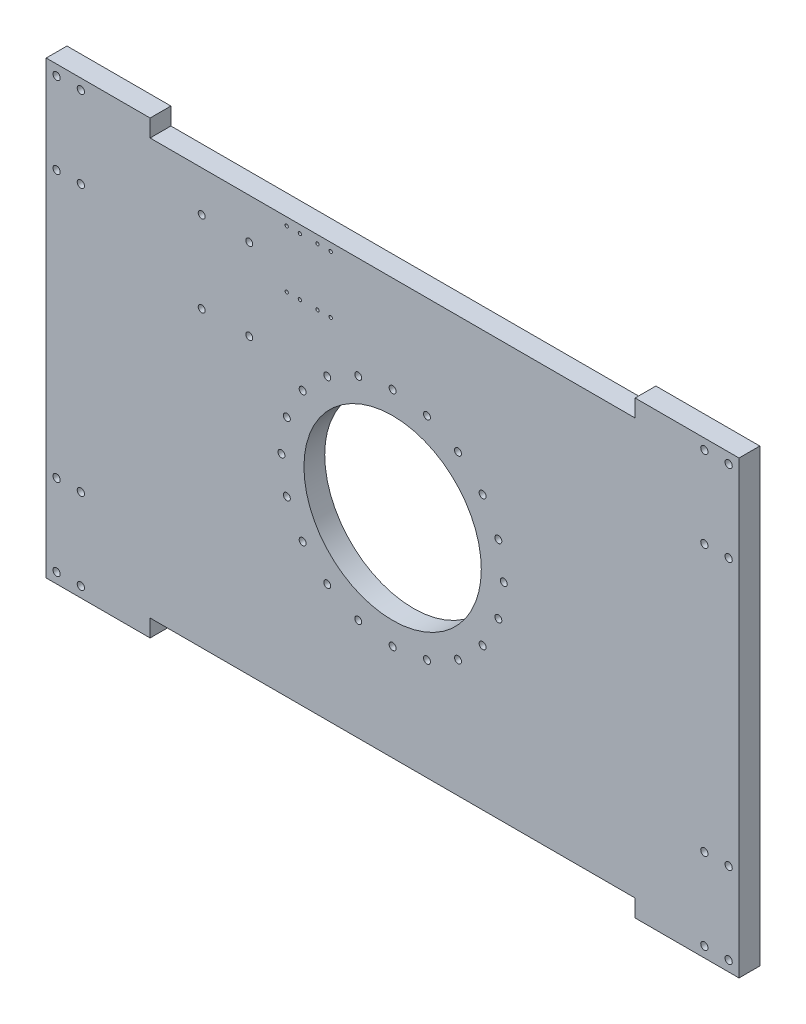
SolidWorks part; units mm, degrees
material "ASTM A36 Acier"
ref_plane "Plan de face" through (0, 0, 0) normal (0, 0, 1) x (1, 0, 0)
ref_plane "Plan de dessus" through (0, 0, 0) normal (0, 1, 0) x (1, 0, 0)
ref_plane "Plan de droite" through (0, 0, 0) normal (1, 0, 0) x (0, 0, -1)
sketch "Esquisse1" plane through (0, 0, 0) normal (0, 0, 1) x (1, 0, 0)
  line L0 (-1000, 1250) -> (-700, 1250)
  line L1 (-700, 1250) -> (-700, 1200)
  line L2 (-700, 1200) -> (700, 1200)
  line L3 (700, 1200) -> (700, 1250)
  line L4 (700, 1250) -> (1000, 1250)
  line L5 (1000, 1250) -> (1000, -50)
  line L6 (1000, -50) -> (700, -50)
  line L7 (700, -50) -> (700, 0)
  line L8 (700, 0) -> (-700, 0)
  line L9 (-700, 0) -> (-700, -50)
  line L10 (-700, -50) -> (-1000, -50)
  line L11 (-1000, -50) -> (-1000, 1250)
  line L13 (-970, -20) -> (-900, -20) construction
  line L14 (-970, -20) -> (-970, 215) construction
  line L15 (-970, 215) -> (-900, 215) construction
  line L16 (-900, -20) -> (-900, 215) construction
  circle A0 centre (-970, -20) radius 10.5
  circle A1 centre (-970, 215) radius 10.5
  circle A2 centre (-900, 215) radius 10.5
  circle A3 centre (-900, -20) radius 10.5
  point P15 (0, 0)
  dimension "D3" = 30
  dimension "D14" = 21
  dimension "D15" = 21
  dimension "D16" = 21
  dimension "D17" = 21
  dimension "D1" = 2000
  dimension "D2" = 50
  dimension "D4" = 300
  dimension "D5" = 300
  dimension "D6" = 300
  dimension "D7" = 300
  dimension "D8" = 1200
  dimension "D9" = 50
  dimension "D10" = 1400
  dimension "D11" = 30
  dimension "D12" = 70
  dimension "D13" = 235
extrude "Boss.-Extru.1" add sketch "Esquisse1" along normal blind 60
sketch "Esquisse2" plane through (0, 0, 60) normal (0, 0, 1) x (1, 0, 0)
  line L0 (700, -50) -> (1000, -50) construction
  circle A0 centre (0, 600) radius 256
  dimension "D1" = 512
  dimension "D2" = 650
extrude "Enlèv. mat.-Extru.1" cut sketch "Esquisse2" against normal through all
sketch "Esquisse4" plane through (0, 0, 0) normal (1, 0, 0) x (0, 0, -1)
  line L0 (0, 600) -> (1429.3387, 600) construction
  dimension "D1" = 600
sketch "Esquisse5" plane through (0, 0, 0) normal (0, 0, 1) x (1, 0, 0)
  circle A0 centre (0, 921) radius 10
  circle A1 centre (0, 600) radius 256 construction
  dimension "D1" = 20
  dimension "D2" = 321
extrude "Enlèv. mat.-Extru.3" cut sketch "Esquisse5" along normal through all
pattern_circular "Répétition circulaire1" count 20 every 18 about axis through (0, 600, 0) along (0, 0, -1) of "Enlèv. mat.-Extru.3"
ref_plane "Plan1" through (0, 0, 0) normal (0, 0, -1) x (-1, 0, 0)
ref_plane "Plan2" through (-1000, -50, 60) normal (0, -1, 0) x (-1, 0, 0)
sketch "Esquisse11" plane through (0, 0, 0) normal (0, 0, -1) x (-1, 0, 0)
  circle A0 centre (413.85, 847.5) radius 10
  circle A1 centre (551.15, 847.5) radius 10
  circle A2 centre (551.15, 1082.5) radius 10
  circle A3 centre (413.85, 1082.5) radius 10
extrude "Enlèv. mat.-Extru.5" cut sketch "Esquisse11" against normal blind 100 and the other way through all
sketch "Esquisse12" plane through (0, 0, 0) normal (0, 0, -1) x (-1, 0, 0)
  circle A0 centre (178.7481, 1177.1251) radius 4.7625
  circle A1 centre (267.6481, 1177.1251) radius 4.7625
  circle A2 centre (178.7481, 1012.0251) radius 4.7625
  circle A3 centre (216.8481, 1012.0251) radius 4.7625
  circle A4 centre (267.6481, 1012.0251) radius 4.7641
  circle A5 centre (305.7481, 1012.0251) radius 4.7625
  circle A6 centre (305.7481, 1177.1251) radius 4.7625
  circle A7 centre (216.8481, 1177.1251) radius 4.7625
extrude "Enlèv. mat.-Extru.6" cut sketch "Esquisse12" against normal blind 100
sketch "Esquisse15" plane through (0, 0, 0) normal (0, 0, -1) x (-1, 0, 0)
  line L0 (1000, 1250) -> (1000, -50) construction
  line L5 (700, 1250) -> (1000, 1250) construction
  circle A0 centre (970, 1220) radius 10.5
  circle A1 centre (970, 985) radius 10.5
  circle A2 centre (900, 985) radius 10.5
  circle A3 centre (900, 1220) radius 10.5
  dimension "D1" = 21
  dimension "D4" = 30
  dimension "D2" = 235
  dimension "D3" = 70
  dimension "D5" = 30
  dimension "D6" = 30
  dimension "D7" = 100
extrude "Enlèv. mat.-Extru.7" cut sketch "Esquisse15" against normal blind 110
mirror "Symétrie1" about plane through (0, 0, 0) normal (1, 0, 0) of "Enlèv. mat.-Extru.7"
sketch "Esquisse16" plane through (0, 0, 0) normal (0, 0, -1) x (-1, 0, 0)
  line L0 (-700, -50) -> (-1000, -50) construction
  line L5 (-1000, -50) -> (-1000, 1250) construction
  circle A0 centre (-970, -20) radius 10.5
  circle A1 centre (-900, -20) radius 10.5
  circle A2 centre (-900, 215) radius 10.5
  circle A3 centre (-970, 215) radius 10.5
  dimension "D1" = 235
  dimension "D3" = 30
  dimension "D2" = 70
  dimension "D4" = 0
  dimension "D5" = 30
extrude "Enlèv. mat.-Extru.8" cut sketch "Esquisse16" against normal blind 110
